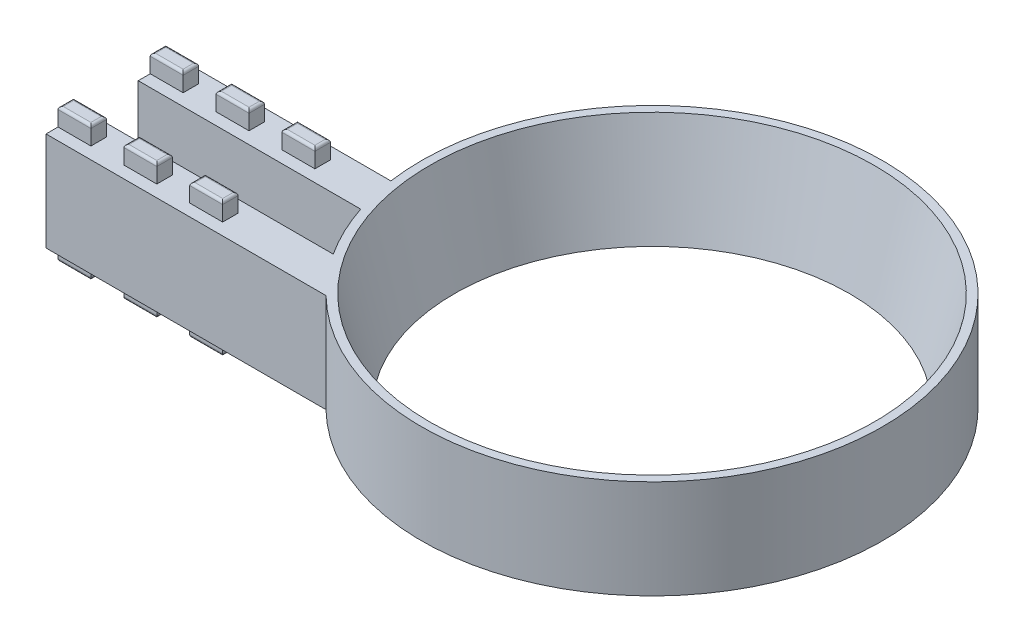
SolidWorks part; units mm, degrees
ref_plane "Front Plane" through (0, 0, 0) normal (0, 0, 1) x (1, 0, 0)
ref_plane "Top Plane" through (0, 0, 0) normal (0, 1, 0) x (1, 0, 0)
ref_plane "Right Plane" through (0, 0, 0) normal (1, 0, 0) x (0, 0, -1)
sketch "Sketch1" plane through (0, 0, 0) normal (0, 1, 0) x (1, 0, 0)
  line L0 (0, 0) -> (-44.45, 0) construction
  circle A0 centre (0, 0) radius 44.45
  point P6 (0, 0)
  point P9 (-540.0888, 252.684)
  point P10 (0, 0)
  dimension "D1" = 88.9
extrude "Boss-Extrude1" add sketch "Sketch1" along normal blind 19.05 contours A0
sketch "Sketch3" plane through (0, 0, 0) normal (0, -1, 0) x (1, 0, 0)
  line L0 (0, 0) -> (-44.45, 0) construction
  line L1 (-31.1085, 31.75) -> (-85.09, 31.75)
  line L2 (-85.09, 31.75) -> (-85.09, 6.35)
  line L3 (-85.09, 6.35) -> (-43.9941, 6.35)
  circle A0 centre (0, 0) radius 44.45 construction
  arc A1 (-43.9941, 6.35) -> (-31.1085, 31.75) centre (0, 0) cw
  point P7 (0, 0)
  point P10 (-42.5971, -12.7)
  point P12 (-20.2893, 0)
  point P13 (0, 0)
  point P14 (0, 0)
  dimension "D1" = 25.4
  dimension "D2" = 40.64
  dimension "D3" = 31.75
extrude "Boss-Extrude2" add sketch "Sketch3" against normal blind 3.175 contours L3 A1 L1 L2
sketch "Sketch4" plane through (0, 0, 31.75) normal (0, 0, 1) x (1, 0, 0)
  line L0 (-85.09, 3.175) -> (-85.09, 19.05)
  line L1 (-85.09, 19.05) -> (-31.1085, 19.05)
  line L2 (44.45, 19.05) -> (-44.45, 19.05) construction
  line L3 (-31.1085, 19.05) -> (-31.1085, 3.175)
  line L4 (-31.1085, 3.175) -> (-85.09, 3.175) construction
  line L5 (-31.1085, 3.175) -> (-85.09, 3.175)
  line L6 (-31.1085, 3.175) -> (-43.9941, 3.175) construction
  line L7 (-31.1085, 3.175) -> (-31.1085, 0) construction
  point P3 (-85.09, 17.6143)
  point P10 (0, 0)
  point P11 (0, 0)
  point P12 (-45.6965, 19.05)
  point P13 (0, 0)
  point P14 (0, 0)
sketch "Sketch5" plane through (0, 0, 6.35) normal (0, 0, -1) x (-1, 0, 0)
  line L0 (85.09, 3.175) -> (85.09, 19.05)
  line L1 (85.09, 19.05) -> (31.1085, 19.05)
  line L2 (31.1085, 19.05) -> (31.1085, 3.175)
  line L3 (31.1085, 3.175) -> (85.09, 3.175)
  line L4 (44.45, 19.05) -> (-44.45, 19.05) construction
  point P3 (0, 0)
extrude "Boss-Extrude3" add sketch "Sketch4" against normal blind 7.62
extrude "Boss-Extrude4" add sketch "Sketch5" against normal blind 7.62
sketch "Sketch2" plane through (0, 0, 0) normal (0, -1, 0) x (1, 0, 0)
  circle A0 centre (0, 0) radius 38.1
  dimension "D1" = 76.2
extrude "Cut-Extrude1" cut sketch "Sketch2" against normal through all draft 14 draft outward yes
ref_plane "Plane1" through (0, 0, 19.05) normal (0, 0, 1) x (1, 0, 0)
ref_plane "Plane2" through (0, 9.525, 0) normal (0, 1, 0) x (1, 0, 0)
sketch "Sketch6" plane through (0, 19.05, 0) normal (0, 1, 0) x (1, 0, 0)
  line L0 (-85.09, -24.13) -> (-85.09, -31.75) construction
  line L1 (-85.09, -29.4386) -> (-78.74, -29.4386)
  line L2 (-85.09, -29.4386) -> (-85.09, -26.4414)
  line L3 (-85.09, -26.4414) -> (-78.74, -26.4414)
  line L4 (-78.74, -29.4386) -> (-78.74, -26.4414)
  line L5 (-72.39, -29.4386) -> (-72.39, -26.4414)
  line L6 (-72.39, -29.4386) -> (-66.04, -29.4386)
  line L7 (-66.04, -29.4386) -> (-66.04, -26.4414)
  line L8 (-72.39, -26.4414) -> (-66.04, -26.4414)
  line L9 (-59.69, -29.4386) -> (-59.69, -26.4414)
  line L10 (-59.69, -29.4386) -> (-53.34, -29.4386)
  line L11 (-53.34, -29.4386) -> (-53.34, -26.4414)
  line L12 (-59.69, -26.4414) -> (-53.34, -26.4414)
  line L13 (-8.7312, -19.05) -> (8.7312, -19.05) construction
  line L14 (-59.69, -8.6614) -> (-53.34, -8.6614)
  line L15 (-53.34, -8.6614) -> (-53.34, -11.6586)
  line L16 (-59.69, -11.6586) -> (-53.34, -11.6586)
  line L17 (-59.69, -8.6614) -> (-59.69, -11.6586)
  line L18 (-72.39, -8.6614) -> (-66.04, -8.6614)
  line L19 (-66.04, -8.6614) -> (-66.04, -11.6586)
  line L20 (-72.39, -11.6586) -> (-66.04, -11.6586)
  line L21 (-72.39, -8.6614) -> (-72.39, -11.6586)
  line L22 (-85.09, -11.6586) -> (-78.74, -11.6586)
  line L23 (-78.74, -8.6614) -> (-78.74, -11.6586)
  line L24 (-85.09, -8.6614) -> (-78.74, -8.6614)
  line L25 (-85.09, -8.6614) -> (-85.09, -11.6586)
  point P6 (-85.09, -27.94)
  point P7 (-85.09, -27.94)
  dimension "D1" = 2.9972
  dimension "D2" = 6.35
  dimension "D3" = 3
  dimension "D4" = 6.35
extrude "Boss-Extrude5" add sketch "Sketch6" along normal blind 3.429
fillet "Fillet1" radius 0.508 24 edges at (-81.915, 22.479, 8.6614) (-78.74, 22.479, 10.16) (-81.915, 22.479, 11.6586) (-85.09, 22.479, 10.16) (-69.215, 22.479, 8.6614) (-66.04, 22.479, 10.16) (-69.215, 22.479, 11.6586) (-72.39, 22.479, 10.16) (-56.515, 22.479, 8.6614) (-53.34, 22.479, 10.16) (-56.515, 22.479, 11.6586) (-59.69, 22.479, 10.16) (-59.69, 22.479, 27.94) (-56.515, 22.479, 26.4414) (-53.34, 22.479, 27.94) (-56.515, 22.479, 29.4386) (-72.39, 22.479, 27.94) (-69.215, 22.479, 26.4414) (-66.04, 22.479, 27.94) (-69.215, 22.479, 29.4386) (-81.915, 22.479, 26.4414) (-78.74, 22.479, 27.94) (-81.915, 22.479, 29.4386) (-85.09, 22.479, 27.94)
mirror "Mirror1" about plane through (0, 9.525, 0) normal (0, 1, 0) of "Fillet1", "Boss-Extrude5"
ref_plane "Plane3" through (0, 0, -50.8) normal (0, 0, 1) x (1, 0, 0)
